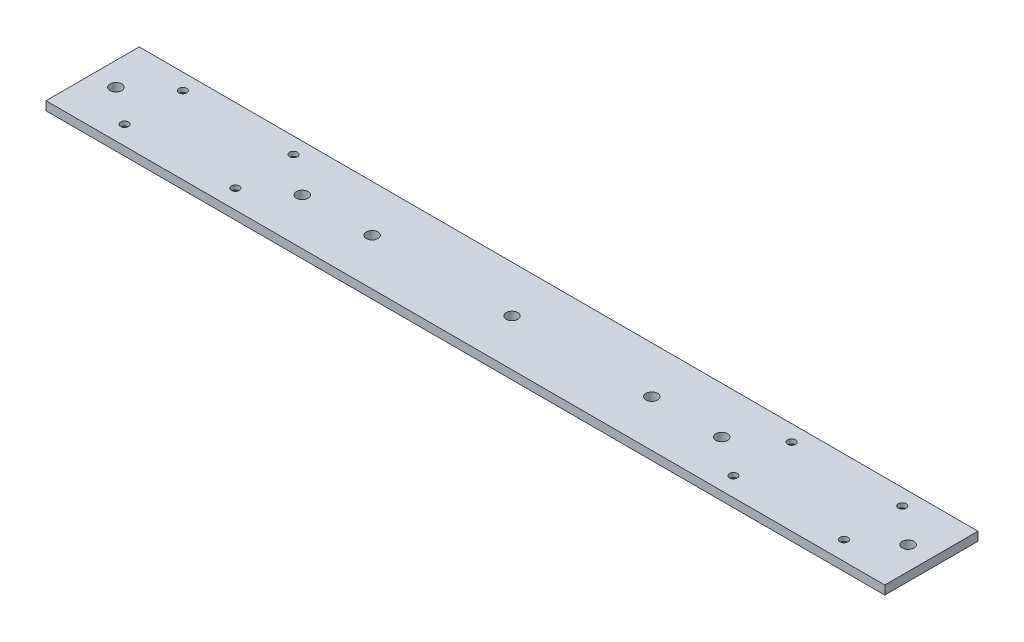
SolidWorks part; units mm, degrees
material "6061 Alloy"
ref_plane "Front Plane" through (0, 0, 0) normal (0, 0, 1) x (1, 0, 0)
ref_plane "Top Plane" through (0, 0, 0) normal (0, 1, 0) x (1, 0, 0)
ref_plane "Right Plane" through (0, 0, 0) normal (1, 0, 0) x (0, 0, -1)
sketch "Sketch1" plane through (0, 0, 0) normal (0, 1, 0) x (1, 0, 0)
  line L1 (0, 0) -> (457.2, 0)
  line L2 (0, 0) -> (0, 50.8)
  line L3 (0, 50.8) -> (457.2, 50.8)
  line L4 (457.2, 0) -> (457.2, 50.8)
  dimension "D1" = 457.2
  dimension "D2" = 50.8
extrude "Boss-Extrude1" add sketch "Sketch1" along normal blind 4.7625
sketch "Sketch2" plane through (0, 4.7625, 0) normal (0, 1, 0) x (1, 0, 0)
  line L0 (0, 0) -> (457.2, 0) construction
  line L1 (0, 50.8) -> (0, 0) construction
  circle A0 centre (12.7, 25.4) radius 3.175
  circle A1 centre (444.5, 25.4) radius 3.175
  dimension "D1" = 25.4
  dimension "D2" = 25.4
  dimension "D3" = 12.7
  dimension "D4" = 444.5
extrude "Cut-Extrude1" cut sketch "Sketch2" against normal blind 244.602
sketch "Sketch3" plane through (0, 4.7625, 0) normal (0, 1, 0) x (1, 0, 0)
  line L0 (457.2, 50.8) -> (0, 50.8) construction
  line L1 (457.2, 0) -> (457.2, 50.8) construction
  circle A0 centre (152.4, 25.4) radius 3.175
  circle A1 centre (304.8, 25.4) radius 3.175
  circle A2 centre (228.6, 25.4) radius 3.175
  dimension "D1" = 25.4
  dimension "D2" = 25.4
  dimension "D3" = 25.4
  dimension "D4" = 76.2
  dimension "D5" = 228.6
  dimension "D6" = 76.2
extrude "Cut-Extrude2" cut sketch "Sketch3" against normal blind 244.602
sketch "Sketch4" plane through (0, 4.7625, 0) normal (0, 1, 0) x (1, 0, 0)
  line L0 (457.2, 50.8) -> (0, 50.8) construction
  line L1 (0, 50.8) -> (0, 0) construction
  line L2 (457.2, 0) -> (457.2, 50.8) construction
  circle A0 centre (114.3, 25.4) radius 3.175
  circle A1 centre (342.9, 25.4) radius 3.175
  dimension "D1" = 25.4
  dimension "D4" = 114.3
  dimension "D2" = 25.4
  dimension "D3" = 114.3
hole_wizard "CSK for #8 Flat Head Machine Screw1" positions "Sketch8" profile "Sketch7" countersink size "#8" standard "ANSI Inch" end condition through all
sketch "Sketch8" plane through (0, 0, 0) normal (0, -1, 0) x (-1, 0, 0)
  point P0 (-424.6625, 42.0688)
  point P3 (-424.6625, 10.3188)
  point P6 (-364.3375, 10.3188)
  point P9 (-364.3375, 42.0688)
  point P12 (-92.8625, 42.0688)
  point P15 (-92.8625, 10.3188)
  point P18 (-32.5375, 10.3188)
  point P21 (-32.5375, 42.0688)
sketch "Sketch7" plane through (424.6625, 0, -42.0688) normal (1, 0, 0) x (0, 0, -1)
  line L0 (0, 0) -> (0, 4.7625)
  line L1 (0, 4.7625) -> (2.1526, 4.7625)
  line L2 (2.1526, 4.7625) -> (2.1526, 2.3741)
  line L3 (2.1526, 2.3741) -> (4.2164, 0)
  line L5 (4.2164, 0) -> (0, 0)
  line L6 (-2.1527, 2.3741) -> (-4.2164, 0) construction
  line L11 (0, -6.35) -> (0, 107.95) construction
  dimension "Thru Hole Dia." = 4.3053
  dimension "Thru Hole Depth" = 4.7625
  dimension "Near C'Sink Dia." = 8.4328
  dimension "Near C'Sink Angle" = 82
extrude "Cut-Extrude3" cut sketch "Sketch4" against normal blind 25.4
